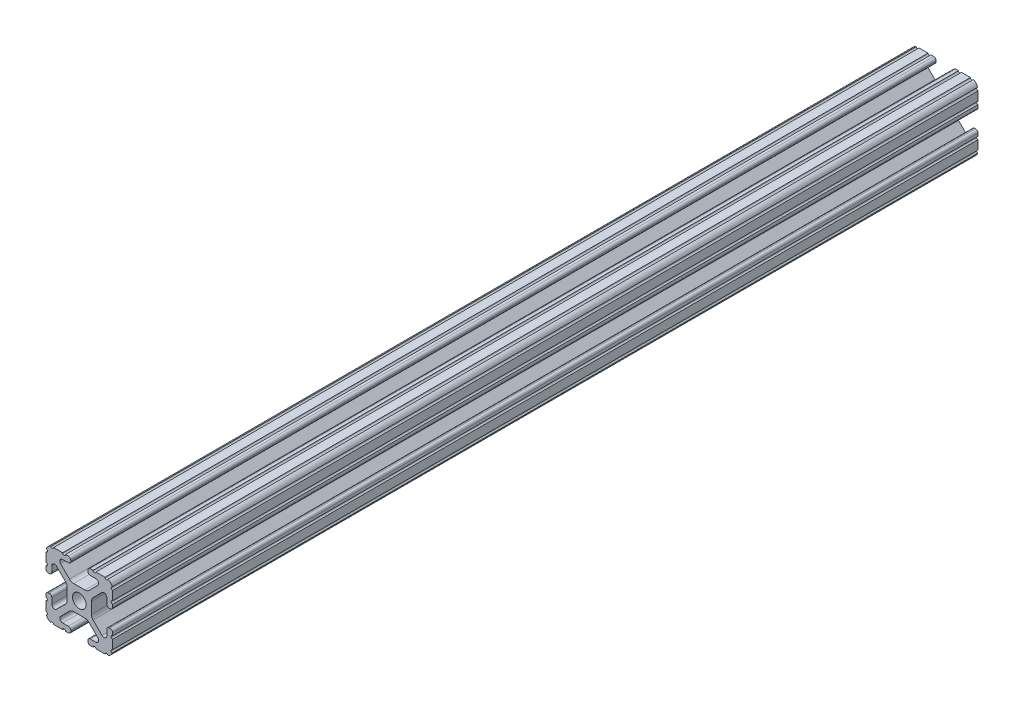
SolidWorks part; units mm, degrees
ref_plane "Front Plane" through (0, 0, 0) normal (0, 0, 1) x (1, 0, 0)
ref_plane "Top Plane" through (0, 0, 0) normal (0, 1, 0) x (1, 0, 0)
ref_plane "Right Plane" through (0, 0, 0) normal (1, 0, 0) x (0, 0, -1)
sketch "Sketch2" plane through (0, 0, 0) normal (0, 0, 1) x (1, 0, 0)
  line L0 (0, 12.7) -> (0, -12.7) construction
  line L1 (-12.7, 0) -> (12.7, 0) construction
  line L2 (3.2512, -12.7) -> (12.7, -12.7)
  line L3 (12.7, -12.7) -> (12.7, -3.2512)
  line L4 (3.2512, -12.7) -> (3.2512, -10.4902)
  line L5 (3.2512, -10.4902) -> (8.9276, -10.4902)
  line L6 (8.9276, -10.4902) -> (3.0856, -4.6482)
  line L7 (0, 0) -> (12.7, -12.7) construction
  line L8 (12.7, -3.2512) -> (10.4902, -3.2512)
  line L9 (10.4902, -3.2512) -> (10.4902, -8.9276)
  line L10 (10.4902, -8.9276) -> (4.6482, -3.0856)
  circle A0 centre (0, 0) radius 2.6035
  arc A1 (6.3485, -10.4902) -> (7.1039, -8.6665) centre (6.3485, -9.4219) ccw construction
  point P8 (0, -4.6482)
  dimension "Center Hole Diameter" = 5.207
  dimension "Rail Height" = 25.4
  dimension "Rail Width" = 25.4
  dimension "T-Slot Width" = 6.5024
  dimension "Slot Inner Width" = 14.8336
  dimension "Thickness" = 2.2098
  dimension "Slot Depth" = 5.842
  dimension "D1" = 2.2098
sketch "Sketch3" plane through (0, 0, 0) normal (1, 0, 0) x (0, 0, -1)
  line L0 (-228.6, -12.7) -> (228.6, -12.7) construction
  line L1 (-205.74, 0) -> (205.74, 0) construction
  dimension "Length" = 457.2
  dimension "D1" = 411.48
sketch "Sketch4" plane through (0, 0, 0) normal (0, 0, 1) x (1, 0, 0)
  line L0 (4.1904, -12.7) -> (10.1173, -12.7)
  line L1 (3.2512, -12.7) -> (12.7, -12.7) construction
  line L2 (3.2512, -12.7) -> (3.2512, -10.4902) construction
  line L3 (3.2512, -10.4902) -> (8.9276, -10.4902) construction
  line L4 (3.2512, -11.4294) -> (3.2512, -11.7608)
  line L5 (4.1904, -10.4902) -> (6.3485, -10.4902)
  line L6 (0, -4.6482) -> (2.164, -4.6482)
  line L7 (8.9276, -10.4902) -> (3.0856, -4.6482) construction
  line L8 (3.7373, -5.2999) -> (7.1039, -8.6665)
  line L9 (12.7, -12.7) -> (12.7, -3.2512) construction
  line L10 (10.4902, -8.9276) -> (4.6482, -3.0856) construction
  line L11 (10.4902, -3.2512) -> (10.4902, -8.9276) construction
  line L12 (10.4902, -6.3485) -> (10.4902, -4.1904)
  line L13 (12.7, -3.2512) -> (10.4902, -3.2512) construction
  line L14 (11.4294, -3.2512) -> (11.7608, -3.2512)
  line L15 (12.7, -4.1904) -> (12.7, -10.1173)
  line L16 (8.6665, -7.1039) -> (5.2999, -3.7373)
  line L17 (4.6482, 0) -> (4.6482, -2.164)
  line L18 (-12.7, 0) -> (12.7, 0) construction
  line L19 (0, -4.6482) -> (0, -2.6035)
  line L20 (0, 12.7) -> (0, -12.7) construction
  line L21 (4.6482, 0) -> (2.6035, 0)
  arc A0 (3.2512, -11.7608) -> (4.1904, -12.7) centre (4.1904, -11.7608) ccw
  arc A2 (3.2512, -11.4294) -> (4.1904, -10.4902) centre (4.1904, -11.4294) cw
  arc A3 (6.3485, -10.4902) -> (7.1039, -8.6665) centre (6.3485, -9.4219) ccw
  arc A4 (2.164, -4.6482) -> (3.7373, -5.2999) centre (2.164, -6.8732) cw
  arc A5 (10.1173, -12.7) -> (12.7, -10.1173) centre (10.1173, -10.1173) ccw
  arc A6 (8.6665, -7.1039) -> (10.4902, -6.3485) centre (9.4219, -6.3485) ccw
  arc A7 (10.4902, -4.1904) -> (11.4294, -3.2512) centre (11.4294, -4.1904) cw
  arc A8 (11.7608, -3.2512) -> (12.7, -4.1904) centre (11.7608, -4.1904) cw
  arc A9 (5.2999, -3.7373) -> (4.6482, -2.164) centre (6.8732, -2.164) cw
  circle A10 centre (0, 0) radius 2.6035 construction
  arc A11 (0, -2.6035) -> (2.6035, 0) centre (0, 0) ccw
  dimension "D1" = 2.5827
  dimension "D2" = 2.225
  dimension "D3" = 0.9392
extrude "Boss-Extrude1" add sketch "Sketch4" along normal mid plane 330.2
sketch "Sketch5" plane through (0, 0, 0) normal (0, 0, 1) x (1, 0, 0)
  line L0 (3.2512, -12.7) -> (12.7, -12.7) construction
  line L1 (4.1904, -10.4902) -> (6.3485, -10.4902) construction
  line L3 (0, 0) -> (12.7, -12.7) construction
  line L4 (6.3485, -10.4902) -> (6.3485, -12.7) construction
  line L5 (8.9276, -10.4902) -> (3.0856, -4.6482) construction
  circle A0 centre (10.3562, -12.7) radius 0.5524
  circle A1 centre (5.796, -12.7) radius 0.5524
  circle A2 centre (12.7, -10.3562) radius 0.5524
  circle A3 centre (12.7, -5.796) radius 0.5524
  point P10 (5.2694, -10.4902)
  point P12 (9.4219, -6.3485)
  dimension "D1" = 1.1049
extrude "Cut-Extrude1" cut sketch "Sketch5" against normal through all both and the other way through all
mirror "Mirror1" about plane through (0, 0, 0) normal (1, 0, 0) of bodies 137 134
mirror "Mirror2" about plane through (0, 0, 0) normal (0, 1, 0) of bodies 135
equation "\"D1@Boss-Extrude1\"=\"Length@Sketch3\""
equation "\"D1@Sketch2\"=\"Thickness@Sketch2\""
equation "\"D2@Sketch4\"=\"Slot Inner Width@Sketch2\"*0.15"
equation "\"D1@Sketch4\"=\"D3@Sketch4\"*2.75"
equation "\"D3@Sketch4\"=\"Thickness@Sketch2\"*0.425"
equation "\"D1@Sketch5\"=\"Thickness@Sketch2\"*0.5"
equation "\"D1@Sketch3\"=\"Length@Sketch3\"*0.9"
